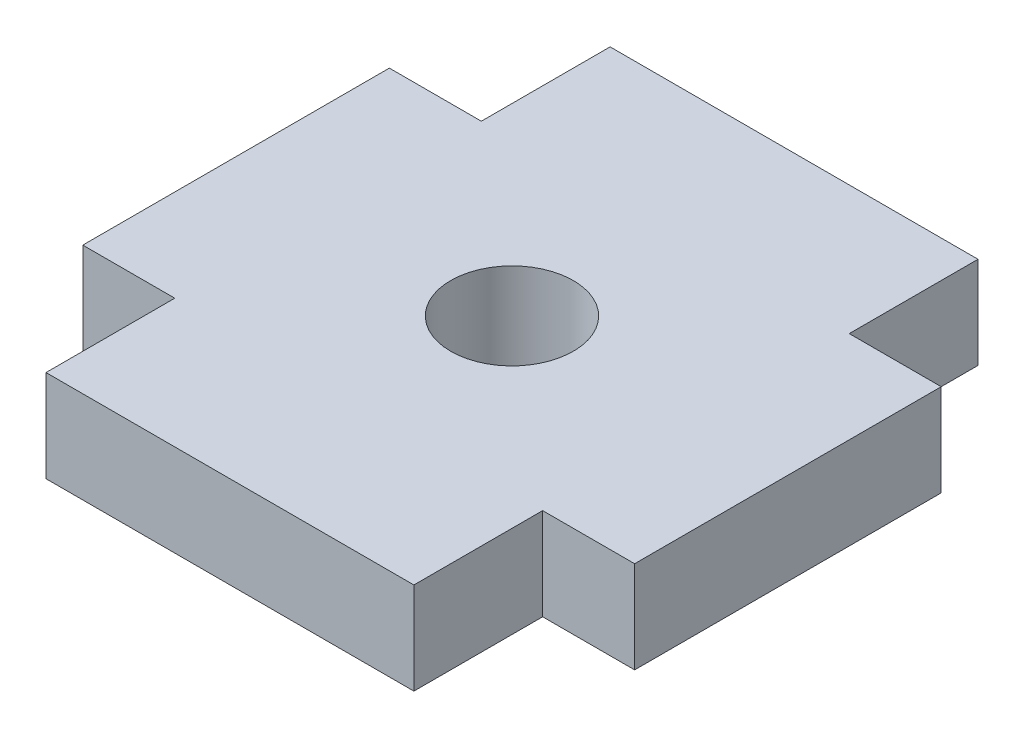
SolidWorks part; units mm, degrees
ref_plane "Plano frontal" through (0, 0, 0) normal (0, 0, 1) x (1, 0, 0)
ref_plane "Plano superior" through (0, 0, 0) normal (0, 1, 0) x (1, 0, 0)
ref_plane "Plano direito" through (0, 0, 0) normal (1, 0, 0) x (0, 0, -1)
ref_plane "Plano1" through (0, 10, 0) normal (0, -1, 0) x (1, 0, 0)
sketch "Esboço1" plane through (0, 10, 0) normal (0, -1, 0) x (1, 0, 0)
  line L0 (-64.5, -9.1999) -> (-64.5, -5)
  line L1 (-64.5, -5) -> (-61.5, -5)
  line L2 (-61.5, -5) -> (-61.5, 5)
  line L3 (-61.5, 5) -> (-64.5, 5)
  line L4 (-64.5, 5) -> (-64.5, 9.1999)
  line L5 (-64.5, 9.1999) -> (-76.5, 9.1999)
  line L6 (-76.5, 9.1999) -> (-76.5, 5)
  line L7 (-76.5, 5) -> (-79.5, 5)
  line L8 (-79.5, 5) -> (-79.5, -5)
  line L9 (-79.5, -5) -> (-76.5, -5)
  line L10 (-76.5, -5) -> (-76.5, -9.1999)
  line L11 (-76.5, -9.1999) -> (-64.5, -9.1999)
  circle A0 centre (-70.5, 0) radius 2
  dimension "D1" = 12
  dimension "D2" = 4.1999
  dimension "D3" = 4.1999
  dimension "D4" = 3
  dimension "D5" = 10
  dimension "D6" = 3
extrude "Ressalto-extrusão1" add sketch "Esboço1" against normal blind 3
